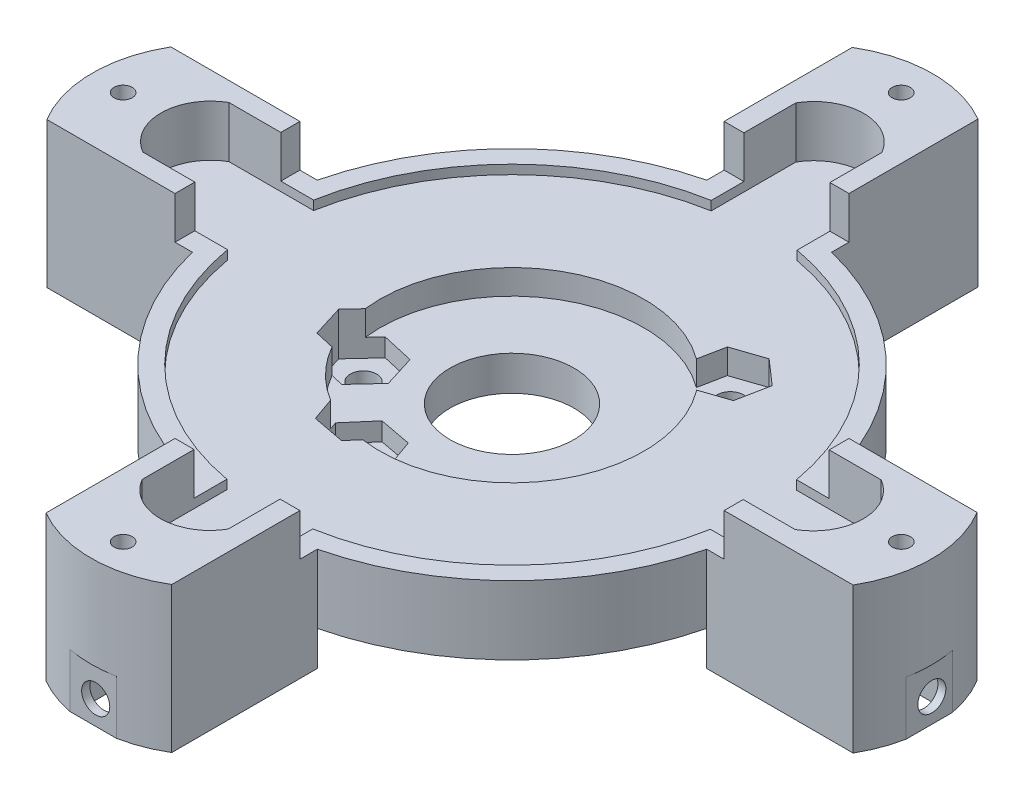
SolidWorks part; units mm, degrees
note: '?' marks a value the reader was unsure of. The reader was unsure of these and kept them because the rebuilt part matched: shared geometry of "Sketch5<3>".
ref_plane "Front Plane" through (0, 0, 0) normal (0, 0, 1) x (1, 0, 0)
ref_plane "Top Plane" through (0, 0, 0) normal (0, 1, 0) x (1, 0, 0)
ref_plane "Right Plane" through (0, 0, 0) normal (1, 0, 0) x (0, 0, -1)
sketch "Sketch1" plane through (0, 0, 0) normal (0, 1, 0) x (1, 0, 0)
  circle A0 centre (0, 0) radius 32
  dimension "D1" = 64
extrude "Boss-Extrude1" add sketch "Sketch1" along normal blind 8.3
sketch "Sketch6" plane through (0, 8.3, 0) normal (0, 1, 0) x (1, 0, 0)
  line L2 (-7.5498, 48.6966) -> (-7.5498, 31.0966)
  line L4 (7.5498, 48.8009) -> (7.5498, 31.0966)
  line L32 (-7.5498, 31.0966) -> (7.5498, 31.0966)
  line L33 (31.0966, 7.5498) -> (31.0966, -7.5498)
  line L34 (48.8009, -7.5498) -> (31.0966, -7.5498)
  line L35 (48.6966, 7.5498) -> (31.0966, 7.5498)
  line L36 (7.5498, -31.0966) -> (-7.5498, -31.0966)
  line L37 (-7.5498, -48.8009) -> (-7.5498, -31.0966)
  line L38 (7.5498, -48.6966) -> (7.5498, -31.0966)
  line L39 (-31.0966, -7.5498) -> (-31.0966, 7.5498)
  line L40 (-48.8009, 7.5498) -> (-31.0966, 7.5498)
  line L41 (-48.6966, -7.5498) -> (-31.0966, -7.5498)
  circle A1 centre (0, 0) radius 32 construction
  arc A2 (7.5498, 48.8009) -> (-7.5498, 48.6966) centre (0.0879, 36.0196) ccw
  arc A12 (48.8009, -7.5498) -> (48.6966, 7.5498) centre (36.0196, -0.0879) ccw
  arc A13 (-7.5498, -48.8009) -> (7.5498, -48.6966) centre (-0.0879, -36.0196) ccw
  arc A14 (-48.8009, 7.5498) -> (-48.6966, -7.5498) centre (-36.0196, 0.0879) ccw
  point P10 (-7.5498, 31.0966)
  point P27 (0, 0)
  dimension "D4" = 29.6
  dimension "D1" = 17.6
  dimension "D2" = 15.1
  dimension "D3" = 4
extrude "Boss-Extrude2" add sketch "Sketch6" along normal blind 5.1 and the other way blind 12.5
sketch "Sketch2" plane through (0, 8.3, 0) normal (0, 1, 0) x (1, 0, 0)
  line L0 (29.2334, -5.2441) -> (39.4793, -5.2441)
  line L2 (5.2441, 29.2334) -> (5.2441, 39.4793)
  line L4 (-5.1559, 29.2491) -> (-5.1559, 39.4793)
  line L5 (0.0441, 42.486) -> (0.0441, 57.8574) construction
  line L6 (29.2491, 5.1559) -> (39.4793, 5.1559)
  line L7 (-5.2441, -29.2334) -> (-5.2441, -39.4793)
  line L8 (5.1559, -29.2491) -> (5.1559, -39.4793)
  line L9 (-29.2334, 5.2441) -> (-39.4793, 5.2441)
  line L10 (-29.2491, -5.1559) -> (-39.4793, -5.1559)
  arc A0 (-5.1559, 29.2491) -> (-29.2334, 5.2441) centre (0, 0) ccw
  arc A1 (5.2441, 39.4793) -> (-5.1559, 39.4793) centre (0.0441, 36.486) ccw
  arc A2 (39.4793, -5.2441) -> (39.4793, 5.1559) centre (36.486, -0.0441) ccw
  arc A3 (-5.2441, -39.4793) -> (5.1559, -39.4793) centre (-0.0441, -36.486) ccw
  arc A4 (-39.4793, 5.2441) -> (-39.4793, -5.1559) centre (-36.486, 0.0441) ccw
  arc A5 (-29.2491, -5.1559) -> (-5.2441, -29.2334) centre (0, 0) ccw
  arc A6 (29.2491, 5.1559) -> (5.2441, 29.2334) centre (0, 0) ccw
  arc A7 (5.1559, -29.2491) -> (29.2334, -5.2441) centre (0, 0) ccw
  point P7 (-5.1559, 29.2491)
  point P28 (0, 0)
  dimension "D1" = 59.4
  dimension "D5" = 12
  dimension "D2" = 4
  dimension "D3" = 10.4
extrude "Cut-Extrude1" cut sketch "Sketch2" against normal blind 1.1 and the other way up to next
sketch "Sketch3" plane through (0, 7.2, 0) normal (0, 1, 0) x (1, 0, 0)
  circle A0 centre (0, 0) radius 15.95
  dimension "D1" = 31.9
extrude "Cut-Extrude2" cut sketch "Sketch3" against normal blind 3
sketch "Sketch4" plane through (0, 4.2, 0) normal (0, 1, 0) x (1, 0, 0)
  circle A0 centre (0, 0) radius 7.5
  dimension "D1" = 15
extrude "Cut-Extrude3" cut sketch "Sketch4" against normal up to next
sketch "Sketch5" plane through (0, 0, 0) normal (0, -1, 0) x (1, 0, 0)
  line L0 (-19.75, 19.75) -> (19.75, -19.75) construction
  line L1 (-19.75, 19.75) -> (19.75, 19.75)
  line L2 (-19.75, 19.75) -> (-19.75, -19.75)
  line L3 (-19.75, -19.75) -> (19.75, -19.75)
  line L4 (19.75, 19.75) -> (19.75, -19.75)
  line L5 (0, 0) -> (0, -19.75) construction
  line L6 (0, 0) -> (19.75, 0) construction
  line L7 (0, 0) -> (13.0574, -13.35) construction
  line L8 (0, 0) -> (0, 19.75) construction
  line L9 (0, 0) -> (-19.75, 0) construction
  circle A0 centre (0, 0) radius 20.3
  circle A1 centre (13.0574, -13.35) radius 1.6
  circle A2 centre (11.817, -12.0818) radius 6
  circle A3 centre (0, 0) radius 18.674 construction
  circle A4 centre (-4.761, 13.3972) radius 1.6
  circle A5 centre (-13.5004, 4.46) radius 1.6
  circle A7 centre (0, 0) radius 31.7
  dimension "D1" = 40.6
  dimension "D3" = 3.2
  dimension "D4" = 12
  dimension "D8" = 3.2
  dimension "D9" = 3.2
  dimension "D2" = 39.5
  dimension "D5" = 14.218
  dimension "D6" = 14.218
  dimension "D7" = 6.4
  dimension "D10" = 12.5
  dimension "D11" = 4.46
extrude "Cut-Extrude4" cut sketch "Sketch5" against normal blind 3
extrude "Cut-Extrude5" cut sketch "Sketch5<3>" against normal up to next contours A1 | A5 | A4
sketch "Sketch5<3>" plane through (0, 0, 0) normal (0, -1, 0) x (1, 0, 0) same geometry as "Sketch5"
sketch "Sketch7" plane through (0, 7.2, 0) normal (0, 1, 0) x (1, 0, 0)
  line L1 (10.0655, 15.9803) -> (9.2835, 12.0741)
  line L2 (9.2835, 12.0741) -> (12.2754, 9.4438)
  line L3 (12.2754, 9.4438) -> (16.0493, 10.7197)
  line L4 (16.0493, 10.7197) -> (16.8313, 14.6259)
  line L5 (16.8313, 14.6259) -> (13.8394, 17.2562)
  line L6 (13.8394, 17.2562) -> (10.0655, 15.9803)
  circle A0 centre (13.0574, 13.35) radius 3.45 construction
  circle A2 centre (0, 0) radius 7.5 construction
  dimension "D1" = 6.9
  dimension "D2" = 19.3
extrude "Cut-Extrude6" cut sketch "Sketch7" against normal up to surface (3 mm away) up to face at (-13.5004, 4.2, 6.06)
sketch "Sketch9" plane through (0, 4.2, 0) normal (0, 1, 0) x (1, 0, 0)
  line L1 (-6.0778, -9.6374) -> (-8.6755, -12.6577)
  line L2 (-8.6755, -12.6577) -> (-7.3587, -16.4175)
  line L3 (-7.3587, -16.4175) -> (-3.4442, -17.157)
  line L4 (-3.4442, -17.157) -> (-0.8465, -14.1367)
  line L5 (-0.8465, -14.1367) -> (-2.1633, -10.3769)
  line L6 (-2.1633, -10.3769) -> (-6.0778, -9.6374)
  line L7 (-10.7939, -1.5368) -> (-14.6786, -0.6545)
  line L8 (-14.6786, -0.6545) -> (-17.3851, -3.5777)
  line L9 (-17.3851, -3.5777) -> (-16.2069, -7.3832)
  line L10 (-16.2069, -7.3832) -> (-12.3221, -8.2655)
  line L11 (-12.3221, -8.2655) -> (-9.6156, -5.3423)
  line L12 (-9.6156, -5.3423) -> (-10.7939, -1.5368)
  circle A0 centre (-4.761, -13.3972) radius 3.45 construction
  circle A1 centre (-13.5004, -4.46) radius 3.45 construction
  circle A2 centre (0, 0) radius 7.5 construction
  dimension "D1" = 11
  dimension "D2" = 10.6
  dimension "D3" = 6.9
  dimension "D4" = 6.9
extrude "Cut-Extrude7" cut sketch "Sketch9" against normal blind 2.2 and the other way up to surface
sketch "Sketch10" plane through (0, 8.3, 0) normal (0, 1, 0) x (1, 0, 0)
  line L0 (0, 0) -> (-39.9223, 0) construction
  line L1 (-33.2, 33.2) -> (33.2, 33.2)
  line L2 (-33.2, 33.2) -> (-33.2, -33.2)
  line L3 (-33.2, -33.2) -> (33.2, -33.2)
  line L4 (33.2, 33.2) -> (33.2, -33.2)
  line L5 (0, 0) -> (0, 46.1219) construction
  dimension "D1" = 66.4
  dimension "D2" = 33.2
  dimension "D3" = 33.2
extrude "Cut-Extrude8" cut sketch "Sketch10" along normal up to next
sketch "Sketch11" plane through (0, 13.4, 0) normal (0, 1, 0) x (1, 0, 0)
  circle A3 centre (0.1405, -47.1674) radius 1.1
  circle A8 centre (-46.9095, -0.1174) radius 1.1
  circle A9 centre (0.1405, 46.9272) radius 1.1
  circle A10 centre (47.1951, -0.1174) radius 1.1
  circle A11 centre (47.1951, -0.1174) radius 1.1 construction
  circle A12 centre (0.1405, -47.1674) radius 1.1 construction
  circle A13 centre (-46.9095, -0.1174) radius 1.1 construction
  circle A17 centre (0.1405, 46.9272) radius 1.1 construction
  point P12 (1.5554, 47.1505)
  point P13 (0.6826, 47.826)
  point P14 (1.5554, 47.1505)
  dimension "D2" = 2.2
  dimension "D4" = 2.2
  dimension "D5" = 2.2
  dimension "D6" = 2.2
  dimension "D11" = 0
  dimension "D3" = 0
  dimension "D7" = 0
  dimension "D8" = 0
extrude "Cut-Extrude9" cut sketch "Sketch11" against normal up to next
sketch "Sketch12" plane through (0, -4.2, 0) normal (0, -1, 0) x (1, 0, 0)
  line L0 (49.5951, -2.5576) -> (44.7951, 2.7924) construction
  line L1 (-49.3095, -2.5326) -> (-44.5095, -2.5326)
  line L2 (-49.3095, -2.5326) -> (-49.3095, 2.7674)
  line L3 (-49.3095, 2.7674) -> (-44.5095, 2.7674)
  line L4 (-44.5095, -2.5326) -> (-44.5095, 2.7674)
  line L5 (-49.3095, -2.5326) -> (-44.5095, 2.7674) construction
  line L6 (-2.5345, -44.5272) -> (2.8155, -49.3272) construction
  line L7 (-2.5345, -44.5272) -> (2.8155, -44.5272)
  line L8 (2.8155, 44.7674) -> (-2.5345, 44.7674)
  line L9 (2.8155, 44.7674) -> (2.8155, 49.5674)
  line L10 (2.8155, 49.5674) -> (-2.5345, 49.5674)
  line L11 (-2.5345, 44.7674) -> (-2.5345, 49.5674)
  line L12 (49.5951, 2.7924) -> (49.5951, -2.5576)
  line L13 (49.5951, 2.7924) -> (44.7951, 2.7924)
  line L14 (44.7951, 2.7924) -> (44.7951, -2.5576)
  line L15 (49.5951, -2.5576) -> (44.7951, -2.5576)
  line L20 (49.5951, 2.7924) -> (44.7951, -2.5576) construction
  line L21 (-2.5345, -44.5272) -> (-2.5345, -49.3272)
  line L22 (-2.5345, -49.3272) -> (2.8155, -49.3272)
  line L23 (-2.5345, 44.7674) -> (2.8155, 49.5674) construction
  line L24 (-2.5345, 49.5674) -> (2.8155, 44.7674) construction
  line L25 (2.8155, -44.5272) -> (2.8155, -49.3272)
  line L26 (2.8155, -44.5272) -> (-2.5345, -49.3272) construction
  circle A0 centre (47.1951, 0.1174) radius 1.1 construction
  circle A2 centre (-46.9095, 0.1174) radius 1.1 construction
  circle A3 centre (0.1405, 47.1674) radius 1.1 construction
  circle A4 centre (0.1405, -46.9272) radius 1.1 construction
  point P5 (0.1405, 47.1674)
  point P8 (-46.9095, 0.1174)
  point P9 (47.1951, 0.1174)
  point P24 (0.2267, 0.217)
  point P26 (0.1405, -46.9272)
  point P27 (-2.4943, 49.2367)
  dimension "D4" = 4.8
  dimension "D5" = 0
  dimension "D7" = 0
  dimension "D1" = 0
  dimension "D2" = 5.3
  dimension "D3" = 4.8
  dimension "D6" = 0
  dimension "D8" = 5.35
  dimension "D9" = 5.35
  dimension "D10" = 4.8
  dimension "D11" = 4.8
  dimension "D12" = 5.35
extrude "Cut-Extrude10" cut sketch "Sketch12" against normal blind 12.6
sketch "Sketch13" plane through (0, -4.2, 0) normal (0, -1, 0) x (1, 0, 0)
  line L0 (6.1555, 31.0966) -> (-6.1555, 31.0966) construction
  line L1 (-3.0095, 42.0966) -> (3.2905, 42.0966)
  line L2 (-3.0095, 42.0966) -> (-3.0095, 39.5966)
  line L3 (-3.0095, 39.5966) -> (3.2905, 39.5966)
  line L4 (3.2905, 42.0966) -> (3.2905, 39.5966)
  line L5 (0.1405, 49.5674) -> (0.1405, 31.0966) construction
  line L6 (2.8155, 49.5674) -> (-2.5345, 49.5674) construction
  line L7 (7.5498, 31.0966) -> (-7.5498, 31.0966) construction
  line L8 (41.7878, 2.85) -> (39.2878, 2.85)
  line L9 (41.7878, 2.85) -> (41.7878, -3.45)
  line L10 (41.7878, -3.45) -> (39.2878, -3.45)
  line L11 (39.2878, 2.85) -> (39.2878, -3.45)
  line L12 (2.5412, -41.9473) -> (2.5412, -39.4473)
  line L13 (2.5412, -41.9473) -> (-3.7588, -41.9473)
  line L14 (-3.7588, -41.9473) -> (-3.7588, -39.4473)
  line L15 (2.5412, -39.4473) -> (-3.7588, -39.4473)
  line L16 (-42.2561, -2.7007) -> (-39.7561, -2.7007)
  line L17 (-42.2561, -2.7007) -> (-42.2561, 3.5993)
  line L18 (-42.2561, 3.5993) -> (-39.7561, 3.5993)
  line L19 (-39.7561, -2.7007) -> (-39.7561, 3.5993)
  point P27 (-0.2342, 0.0747)
  dimension "D1" = 6.3
  dimension "D2" = 2.5
  dimension "D3" = 8.5
  dimension "D4" = 3.15
extrude "Cut-Extrude11" cut sketch "Sketch13" against normal blind 6.5
sketch "Sketch14" plane through (0, -4.2, 0) normal (0, -1, 0) x (1, 0, 0)
  line L0 (7.5498, 31.0966) -> (-7.5498, 31.0966) construction
  line L2 (0.1405, 47.1674) -> (0.1405, 31.0966) construction
  circle A0 centre (0.35, 35.1966) radius 1.7
  circle A1 centre (34.8878, -0.35) radius 1.7
  circle A2 centre (-0.6588, -34.8878) radius 1.7
  circle A3 centre (-35.1966, 0.6588) radius 1.7
  point P16 (-0.1544, 0.1544)
  dimension "D1" = 3.4
  dimension "D2" = 4.1
extrude "Cut-Extrude12" cut sketch "Sketch14" against normal blind 3.5
sketch "Sketch15" plane through (-31.0966, 0, 0) normal (1, 0, 0) x (0, 0, -1)
  line L0 (-7.5498, -4.2) -> (7.5498, -4.2) construction
  line L1 (-3.4498, -0.7) -> (2.8498, -0.7)
  line L2 (-3.4498, -0.7) -> (-3.4498, 1.8)
  line L3 (-3.4498, 1.8) -> (2.8498, 1.8)
  line L4 (2.8498, -0.7) -> (2.8498, 1.8)
  line L5 (-7.5498, -4.2) -> (-7.5498, 0) construction
  line L6 (7.5498, -4.2) -> (7.5498, 0) construction
  dimension "D1" = 3.5
  dimension "D2" = 4.1
  dimension "D3" = 4.7
  dimension "D4" = 2.5
extrude "Cut-Extrude13" cut sketch "Sketch15" against normal blind 7.6
pattern_circular "CirPattern1" count 4 every 90 about axis through (0, 0, 0) along (0, 1, 0) of "Cut-Extrude13"
sketch "Sketch16" plane through (0, -4.2, 0) normal (0, -1, 0) x (1, 0, 0)
  line L0 (50.5524, 2.8879) -> (50.5524, -2.7121)
  line L2 (2.8879, -50.5524) -> (-2.7121, -50.5524)
  line L3 (-50.5524, -2.8879) -> (-50.5524, 2.7121)
  line L4 (-2.8879, 50.5524) -> (2.7121, 50.5524)
  arc A0 (48.6966, -7.5498) -> (48.8009, 7.5498) centre (36.0196, 0.0879) ccw construction
  arc A1 (50.5524, -2.7121) -> (50.5524, 2.8879) centre (36.0196, 0.0879) ccw
  arc A2 (-2.7121, -50.5524) -> (2.8879, -50.5524) centre (0.0879, -36.0196) ccw
  arc A3 (-50.5524, 2.7121) -> (-50.5524, -2.8879) centre (-36.0196, -0.0879) ccw
  arc A4 (2.7121, 50.5524) -> (-2.8879, 50.5524) centre (-0.0879, 36.0196) ccw
  arc A5 (-48.6966, 7.5498) -> (-48.8009, -7.5498) centre (-36.0196, -0.0879) ccw construction
  point P18 (0, 0)
  dimension "D1" = 5.6
  dimension "D2" = 4
extrude "Cut-Extrude14" cut sketch "Sketch16" against normal blind 6.5
sketch "Sketch17" plane through (50.5524, 0, 0) normal (1, 0, 0) x (0, 0, -1)
  line L0 (-2.8879, 2.3) -> (-2.8879, -4.2) construction
  line L1 (-2.8879, -4.2) -> (2.7121, -4.2) construction
  circle A0 centre (0.2121, -1.3) radius 1.7
  dimension "D1" = 3.4
  dimension "D2" = 3.1
  dimension "D3" = 2.9
extrude "Cut-Extrude15" cut sketch "Sketch17" against normal blind 9
ref_axis "Axis1" through (0, 0, 0) along (0, 1, 0)?
pattern_circular "CirPattern9" count 4 every 90 about axis through (0, 0, 0) along (0, 1, 0) of "Cut-Extrude15"
equation "\"D4@Sketch11\"=\"D2@Sketch11\""
equation "\"D5@Sketch11\"=\"D2@Sketch11\""
equation "\"D6@Sketch11\"=\"D2@Sketch11\""
